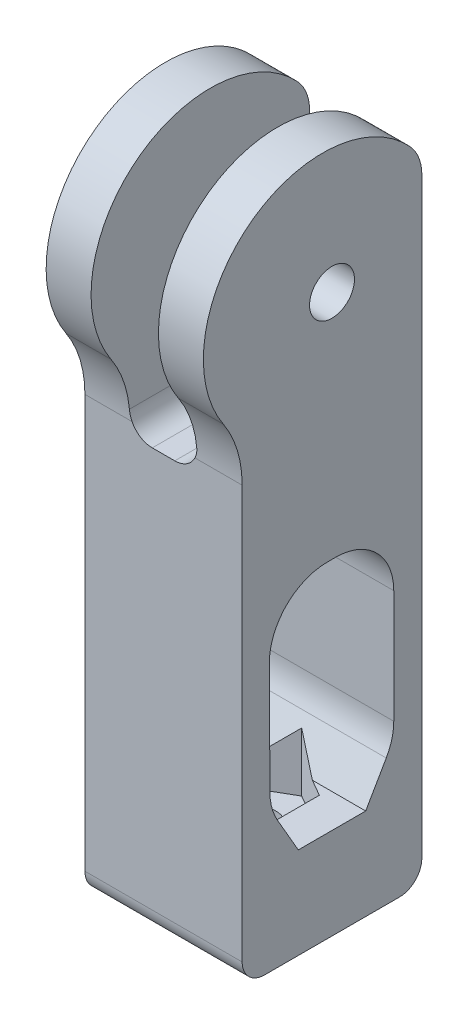
SolidWorks part; units mm, degrees
material "ABS generico"
ref_plane "Piano frontale" through (0, 0, 0) normal (0, 0, 1) x (1, 0, 0)
ref_plane "Piano superiore" through (0, 0, 0) normal (0, 1, 0) x (1, 0, 0)
ref_plane "Piano destro" through (0, 0, 0) normal (1, 0, 0) x (0, 0, -1)
sketch "Sketch9" plane through (0, 0, 0) normal (1, 0, 0) x (0, 0, -1)
  line L0 (8, 5.0539) -> (8, -49.642)
  line L1 (8, -49.642) -> (-8, -49.642)
  line L2 (-8, -49.642) -> (-8, -10.8758)
  line L3 (5.5, -41.5) -> (5.5, -25.7624)
  line L5 (0.3362, -20.5986) -> (-0.4104, -20.5986)
  line L6 (-5.5741, -25.7867) -> (-5.5, -41.5)
  line L7 (-5.5, -41.5) -> (5.5, -41.5)
  line L8 (0, -49.642) -> (0, 21.1385) construction
  circle A0 centre (0, 0) radius 2
  arc A1 (6.9253, 7.782) -> (-9.6743, -5.3367) centre (-0.8371, 0.5427) ccw
  arc A2 (-8, -10.8758) -> (-9.6743, -5.3367) centre (-18, -10.8758) ccw
  arc A3 (8, 5.0539) -> (6.9253, 7.782) centre (4, 5.0539) ccw
  arc A4 (5.5, -25.7624) -> (0.3362, -20.5986) centre (0.3362, -25.7624) ccw
  arc A5 (-5.5741, -25.7867) -> (-0.4104, -20.5986) centre (-0.4104, -25.7624) cw
  point P24 (8, 6.4221)
  dimension "D1" = 4
  dimension "D2" = 10
  dimension "D3" = 4
  dimension "D4" = 5.1638
  dimension "D5" = 16
extrude "Boss-Extrude3" add sketch "Sketch9" along normal blind 14
sketch "Sketch10" plane through (0, -49.642, 0) normal (0, -1, 0) x (1, 0, 0)
  line L0 (7, 8) -> (7, -8) construction
  line L1 (14, 8) -> (0, 8) construction
  line L2 (14, -8) -> (0, -8) construction
  line L3 (0, 0) -> (18.4029, 0) construction
  line L5 (0, 8) -> (0, -8) construction
  circle A0 centre (7, 0) radius 2
  point P11 (7, 0)
  dimension "D1" = 4
extrude "Cut-Extrude7" cut sketch "Sketch10" against normal blind 14
ref_plane "Plane1" through (0, 16, 0) normal (0, 1, 0) x (1, 0, 0)
sketch "Sketch11" plane through (0, 16, 0) normal (0, 1, 0) x (1, 0, 0)
  line L0 (7, 8) -> (7, -11.4514) construction
  line L1 (14, 8) -> (0, 8) construction
  line L2 (0, -11.4514) -> (14, -11.4514) construction
  line L4 (10, -16.0809) -> (4, -16.0809)
  line L5 (10, -16.0809) -> (10, 10.6052)
  line L6 (10, 10.6052) -> (4, 10.6052)
  line L7 (4, -16.0809) -> (4, 10.6052)
  line L8 (10, -16.0809) -> (4, 10.6052) construction
  line L9 (10, 10.6052) -> (4, -16.0809) construction
  point P6 (7, -2.7378)
  dimension "D1" = 6
extrude "Cut-Extrude8" cut sketch "Sketch11" against normal blind 28
fillet "Fillet1" radius 2 2 edges at (7, -49.642, -8) (7, -49.642, 8)
chamfer "Chamfer1" distance 2.5 angle 60 2 edges at (7, -41.5, 5.5) (7, -41.5, -5.5) first distance on face at (7, -41.5, 2)
sketch "Sketch12" plane through (0, -41.5, 0) normal (0, 1, 0) x (1, 0, 0)
  line L1 (7, 4.3) -> (3.2761, 2.15)
  line L2 (3.2761, 2.15) -> (3.2761, -2.15)
  line L3 (3.2761, -2.15) -> (7, -4.3)
  line L4 (7, -4.3) -> (10.7239, -2.15)
  line L5 (10.7239, -2.15) -> (10.7239, 2.15)
  line L6 (10.7239, 2.15) -> (7, 4.3)
  circle A0 centre (7, 0) radius 4.3 construction
extrude "Extrude1" cut sketch "Sketch12" against normal blind 3 and the other way blind 3
fillet "Fillet2" radius 2 2 edges at (4, -12, 0) (10, -12, 0)
fillet "Fillet3" radius 5 2 edges at (7, -37.1699, -5.5) (7, -37.1342, 5.5206)
